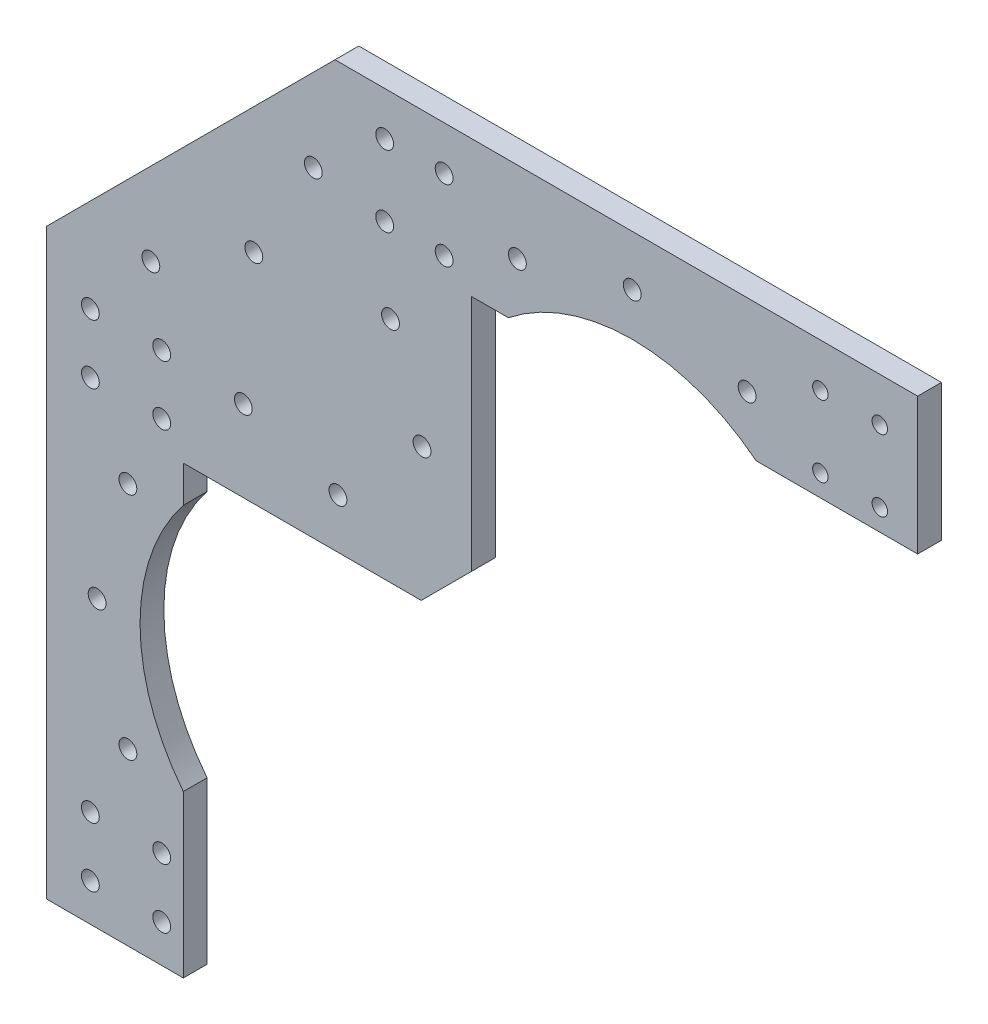
SolidWorks part; units mm, degrees
ref_plane "Front Plane" through (0, 0, 0) normal (0, 0, 1) x (1, 0, 0)
ref_plane "Top Plane" through (0, 0, 0) normal (0, 1, 0) x (1, 0, 0)
ref_plane "Right Plane" through (0, 0, 0) normal (1, 0, 0) x (0, 0, -1)
sketch "Sketch1" plane through (0, 0, 0) normal (0, 0, 1) x (1, 0, 0)
  line L0 (0, 0) -> (0, 75.5) construction
  line L1 (-98.5, -48) -> (-75.5, -48)
  line L2 (-98.5, -48) -> (-98.5, 49.9924)
  line L4 (-75.5, -48) -> (-75.5, 27) construction
  line L5 (-49.9924, 98.5) -> (48, 98.5)
  line L7 (-27, 75.5) -> (48, 75.5) construction
  line L8 (48, 98.5) -> (48, 75.5)
  line L9 (0, 0) -> (-75.5, 0) construction
  line L10 (-27, 75.5) -> (-75.5, 27) construction
  line L11 (-75.5, 75.5) -> (-27, 75.5) construction
  line L12 (-75.5, 27) -> (-75.5, 75.5) construction
  line L13 (-49.9924, 98.5) -> (-98.5, 49.9924)
  line L14 (-98.5, 98.5) -> (-49.9924, 98.5) construction
  line L15 (-98.5, 49.9924) -> (-98.5, 98.5) construction
  line L16 (-20.8425, 75.5) -> (-27, 75.5)
  line L17 (20.8425, 75.5) -> (48, 75.5)
  line L18 (-75.5, 27) -> (-75.5, 20.8425)
  line L19 (-75.5, -48) -> (-75.5, -20.8425)
  line L20 (-75.5, 20.8425) -> (-75.5, -20.8425) construction
  line L21 (-20.8425, 75.5) -> (20.8425, 75.5) construction
  line L22 (-75.5, 27) -> (-35.4853, 27)
  line L23 (-27, 35.4853) -> (-27, 75.5)
  line L24 (-35.4853, 27) -> (-27, 35.4853)
  arc A0 (20.8425, 75.5) -> (-20.8425, 75.5) centre (0, 49.3) ccw
  arc A1 (-75.5, 20.8425) -> (-75.5, -20.8425) centre (-49.3, 0) ccw
  point P16 (-26.7667, 35.0194)
  dimension "D6" = 33.4791
  dimension "D1" = 135
  dimension "D2" = 23
  dimension "D3" = 75.5
  dimension "D4" = 48
  dimension "D5" = 105
  dimension "D7" = 49.3
  dimension "D8" = 27
  dimension "D9" = 12
extrude "Boss-Extrude1" add sketch "Sketch1" along normal blind 4
ref_axis "Axis1" through (0, 0, -0.2) along (0, 0, 1)
sketch "Sketch3" plane through (0, 0, 4) normal (0, 0, 1) x (1, 0, 0)
  line L0 (-91.1351, 41.6359) -> (-91.1351, 31.6359) construction
  line L1 (-91.1351, -31.6359) -> (-91.1351, -41.6359) construction
  line L2 (-91.1351, -31.6359) -> (-79.1351, -31.6359) construction
  line L3 (-79.1351, -31.6359) -> (-79.1351, -41.6359) construction
  line L4 (-91.1351, -41.6359) -> (-79.1351, -41.6359) construction
  line L5 (-91.1351, 41.6359) -> (-79.1351, 41.6359) construction
  line L6 (-79.1351, 41.6359) -> (-79.1351, 31.6359) construction
  line L7 (-91.1351, 31.6359) -> (-79.1351, 31.6359) construction
  line L8 (31.6359, 91.1351) -> (31.6359, 79.1351) construction
  line L9 (31.6359, 91.1351) -> (41.6359, 91.1351) construction
  line L10 (41.6359, 91.1351) -> (41.6359, 79.1351) construction
  line L11 (31.6359, 79.1351) -> (41.6359, 79.1351) construction
  line L12 (-31.6359, 91.1351) -> (-31.6359, 79.1351) construction
  line L13 (-31.6359, 91.1351) -> (-41.6359, 91.1351) construction
  line L14 (-41.6359, 91.1351) -> (-41.6359, 79.1351) construction
  line L15 (-31.6359, 79.1351) -> (-41.6359, 79.1351) construction
  circle A0 centre (-91.1351, -41.6359) radius 1.5
  circle A1 centre (-91.1351, -31.6359) radius 1.5
  circle A2 centre (-79.1351, -31.6359) radius 1.5
  circle A3 centre (-79.1351, -41.6359) radius 1.5
  circle A4 centre (-91.1351, 31.6359) radius 1.5
  circle A5 centre (-91.1351, 41.6359) radius 1.5
  circle A6 centre (-79.1351, 41.6359) radius 1.5
  circle A7 centre (-79.1351, 31.6359) radius 1.5
  circle A8 centre (31.6359, 79.1351) radius 1.3
  circle A9 centre (31.6359, 91.1351) radius 1.3
  circle A10 centre (41.6359, 91.1351) radius 1.3
  circle A11 centre (41.6359, 79.1351) radius 1.3
  circle A12 centre (-31.6359, 79.1351) radius 1.5
  circle A13 centre (-31.6359, 91.1351) radius 1.5
  circle A14 centre (-41.6359, 91.1351) radius 1.5
  circle A15 centre (-41.6359, 79.1351) radius 1.5
  dimension "D1" = 3
  dimension "D2" = 3
  dimension "D3" = 2.6
  dimension "D4" = 3
extrude "Cut-Extrude1" cut sketch "Sketch3" against normal blind 10
sketch "Sketch4" plane through (0, 0, 4) normal (0, 0, 1) x (1, 0, 0)
  line L0 (0, 0) -> (0, 90) construction
  line L1 (0, 0) -> (-63.6396, 63.6396) construction
  line L2 (0, 0) -> (-90, 0) construction
  line L3 (-84.8236, 19.3185) -> (-90, 0) construction
  line L4 (-90, 0) -> (-84.8236, -19.3185) construction
  line L5 (-80.9601, 53.6396) -> (-63.6396, 63.6396) construction
  line L6 (-63.6396, 63.6396) -> (-69.6582, 69.6582) construction
  line L7 (-19.3185, 84.8236) -> (0, 90) construction
  line L8 (-65.4074, 40.6586) -> (-40.6586, 65.4074) construction
  line L9 (-35.3553, 49.4975) -> (-49.4975, 35.3553) construction
  circle A0 centre (-90, 0) radius 1.5
  circle A1 centre (-63.6396, 63.6396) radius 1.5
  circle A2 centre (0, 90) radius 1.5
  circle A3 centre (-80.9601, 53.6396) radius 1.5
  circle A4 centre (-53.6396, 80.9601) radius 1.5
  circle A5 centre (19.3185, 84.8236) radius 1.5
  circle A6 centre (-19.3185, 84.8236) radius 1.5
  circle A7 centre (-84.8236, 19.3185) radius 1.5
  circle A8 centre (-84.8236, -19.3185) radius 1.5
  circle A9 centre (-40.6586, 65.4074) radius 1.5
  circle A10 centre (-65.4074, 40.6586) radius 1.5
  circle A11 centre (-49.4975, 35.3553) radius 1.5
  circle A12 centre (-35.3553, 49.4975) radius 1.5
  dimension "D2" = 3
  dimension "D1" = 45
  dimension "D3" = 90
  dimension "D4" = 75
  dimension "D5" = 20
  dimension "D6" = 90
  dimension "D7" = 75
  dimension "D8" = 75
  dimension "D9" = 35
  dimension "D10" = 20
  dimension "D11" = 15
  dimension "D12" = 15
extrude "Cut-Extrude2" cut sketch "Sketch4" against normal through all
